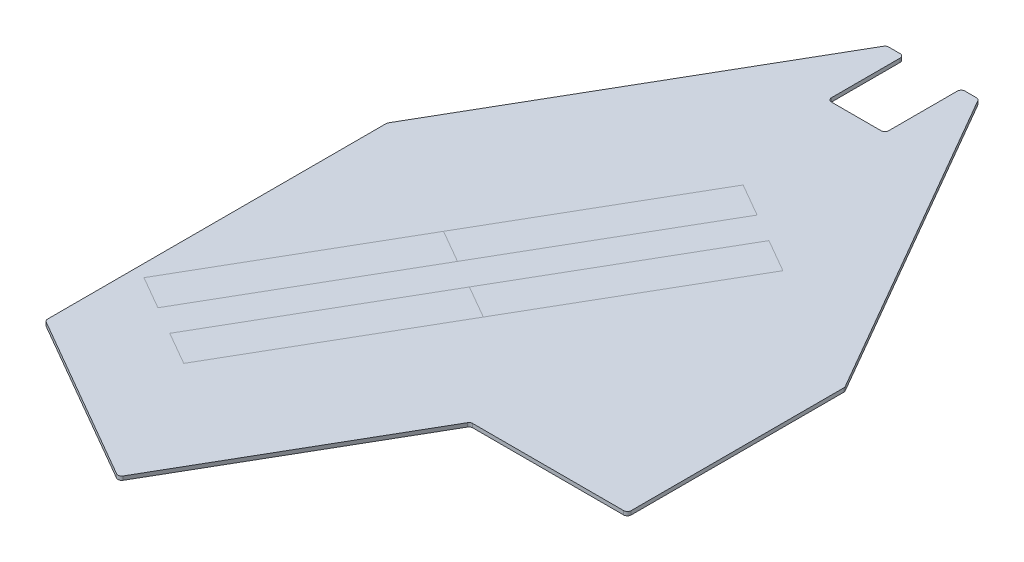
SolidWorks part; units mm, degrees
material "1.0116 (S235J2G3)"
ref_plane "Front Plane" through (0, 0, 0) normal (0, 0, 1) x (1, 0, 0)
ref_plane "Top Plane" through (0, 0, 0) normal (0, 1, 0) x (1, 0, 0)
ref_plane "Right Plane" through (0, 0, 0) normal (1, 0, 0) x (0, 0, -1)
sketch "Sketch1" plane through (0, 0, 0) normal (0, 1, 0) x (1, 0, 0)
  line L0 (0, 0) -> (0, 1800) construction
  line L1 (590, 0) -> (194.4486, 0)
  line L2 (-600, 0) -> (-600, 567.3205)
  line L3 (-598.6603, 572.3205) -> (-123.686, 1395)
  line L4 (-115.0258, 1400) -> (-85, 1400)
  line L5 (-75, 1390) -> (-75, 1210)
  line L6 (-65, 1200) -> (65, 1200)
  line L7 (75, 1390) -> (75, 1210)
  line L8 (115.0258, 1400) -> (85, 1400)
  line L9 (598.6603, 572.3205) -> (123.686, 1395)
  line L10 (600, 10) -> (600, 567.3205)
  line L13 (-144.675, -577.3794) -> (185.7884, -5)
  line L14 (-158.3353, -581.0397) -> (-595, -328.9312)
  line L15 (-600, -320.2709) -> (-600, 0)
  arc A0 (-600, 567.3205) -> (-598.6603, 572.3205) centre (-590, 567.3205) cw
  arc A1 (-595, -328.9312) -> (-600, -320.2709) centre (-590, -320.2709) cw
  arc A2 (-158.3353, -581.0397) -> (-144.675, -577.3794) centre (-153.3353, -572.3794) ccw
  arc A3 (-123.686, 1395) -> (-115.0258, 1400) centre (-115.0258, 1390) cw
  arc A4 (185.7884, -5) -> (194.4486, 0) centre (194.4486, -10) cw
  arc A5 (600, 10) -> (590, 0) centre (590, 10) cw
  arc A6 (598.6603, 572.3205) -> (600, 567.3205) centre (590, 567.3205) cw
  arc A7 (115.0258, 1400) -> (123.686, 1395) centre (115.0258, 1390) cw
  arc A8 (75, 1210) -> (65, 1200) centre (65, 1210) cw
  arc A9 (-75, 1210) -> (-65, 1200) centre (-65, 1210) ccw
  arc A10 (75, 1390) -> (85, 1400) centre (85, 1390) cw
  arc A11 (-85, 1400) -> (-75, 1390) centre (-85, 1390) cw
  point P3 (-100.0129, 1400)
  point P11 (0, 1200)
  point P20 (-600, 570)
  point P23 (-600, -326.0445)
  point P26 (-149.675, -586.0397)
  point P29 (-120.7993, 1400)
  point P32 (188.6751, 0)
  point P35 (600, 0)
  point P38 (600, 570)
  point P41 (120.7993, 1400)
  point P44 (75, 1200)
  point P47 (-75, 1200)
  point P50 (75, 1400)
  point P53 (-75, 1400)
  dimension "D13" = 10
  dimension "D14" = 10
  dimension "D15" = 10
  dimension "D1" = 1800
  dimension "D2" = 600
  dimension "D3" = 570
  dimension "D4" = 1400
  dimension "D5" = 75
  dimension "D6" = 60
  dimension "D7" = 200
  dimension "D8" = 90
  dimension "D9" = 326.0445
  dimension "D10" = 120
  dimension "D11" = 411.3249
  dimension "D12" = 450.325
extrude "Boss-Extrude2" add sketch "Sketch1" along normal blind 10
sketch "Sketch2" plane through (0, 0, 0) normal (0, -1, 0) x (-1, 0, 0)
  line L0 (-600, 34.34) -> (600, 34.34)
  line L1 (-600, 10) -> (-600, 567.3205) construction
  line L2 (600, 0) -> (600, 567.3205) construction
  line L3 (600, 34.34) -> (600, 94.34)
  line L4 (600, 94.34) -> (-600, 94.34)
  line L5 (-600, 94.34) -> (-600, 34.34)
  line L6 (-590, 0) -> (-194.4486, 0) construction
  line L7 (-75, 1366.1467) -> (-600, 456.82)
  line L8 (-75, 1390) -> (-75, 1210) construction
  line L9 (-600, 456.82) -> (-600, 336.82)
  line L10 (-600, 336.82) -> (-75, 1246.1467)
  line L11 (-75, 1246.1467) -> (-75, 1366.1467)
  line L12 (-598.6603, 572.3205) -> (-123.686, 1395) construction
  line L13 (0, -747.4199) -> (0, 2106.0652) construction
  line L14 (600, 336.82) -> (75, 1246.1467)
  line L15 (600, 456.82) -> (600, 336.82)
  line L16 (75, 1366.1467) -> (600, 456.82)
  line L17 (75, 1246.1467) -> (75, 1366.1467)
  dimension "D1" = 94.34
  dimension "D2" = 34.34
  dimension "D3" = 60
  dimension "D4" = 56.59
split line "Split Line1"
sketch "Sketch3" plane through (0, 10, 0) normal (0, 1, 0) x (1, 0, 0)
  line L0 (-320.8032, -242.4423) -> (254.1968, 753.4869)
  line L1 (254.1968, 753.4869) -> (167.5943, 803.4869)
  line L2 (167.5943, 803.4869) -> (-407.4057, -192.4423)
  line L3 (-407.4057, -192.4423) -> (-320.8032, -242.4423)
  line L4 (-280.1204, 398.0223) -> (-193.5179, 348.0223)
  line L5 (-481.0179, -149.9423) -> (93.9821, 845.9869)
  line L6 (93.9821, 845.9869) -> (7.3796, 895.9869)
  line L7 (7.3796, 895.9869) -> (-567.6204, -99.9423)
  line L8 (-567.6204, -99.9423) -> (-481.0179, -149.9423)
  line L9 (-119.9057, 305.5223) -> (-33.3032, 255.5223)
  line L10 (-598.6603, 572.3205) -> (-123.686, 1395) construction
  line L11 (-144.675, -577.3794) -> (185.7884, -5) construction
  line L12 (-158.3353, -581.0397) -> (-595, -328.9312) construction
  dimension "D1" = 100
  dimension "D2" = 1150
  dimension "D3" = 100
  dimension "D4" = 85
  dimension "D5" = 320
  dimension "D6" = 212
  dimension "D7" = 212
  dimension "D8" = 1150
split line "Split Line2"
